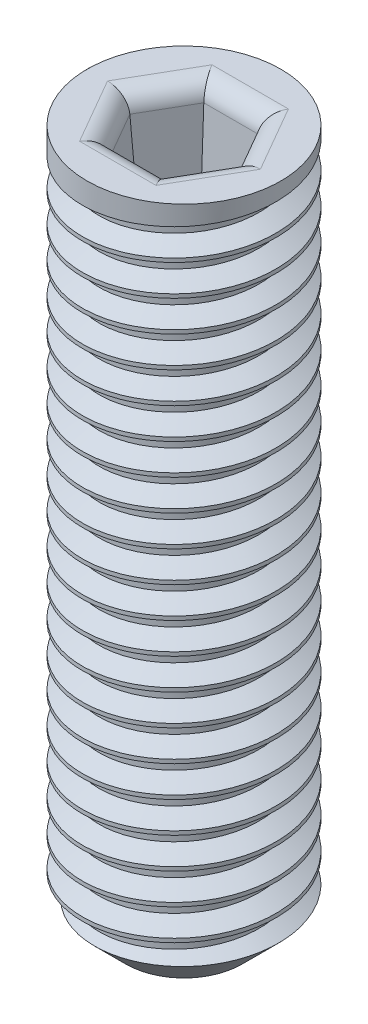
SolidWorks part; units mm, degrees
material "Cast Stainless Steel"
ref_plane "Front Plane" through (0, 0, 0) normal (0, 0, 1) x (1, 0, 0)
ref_plane "Top Plane" through (0, 0, 0) normal (0, 1, 0) x (1, 0, 0)
ref_plane "Right Plane" through (0, 0, 0) normal (1, 0, 0) x (0, 0, -1)
sketch "Sketch1" plane through (0, 0, 0) normal (0, 1, 0) x (1, 0, 0)
  circle A0 centre (0, 0) radius 2.5
  dimension "D1" = 5
extrude "Boss-Extrude1" add sketch "Sketch1" along normal blind 18
chamfer "Chamfer1" distance 1 angle 45 1 edges at (0, 0, 2.5)
sketch "Sketch2" plane through (0, 18, 0) normal (0, 1, 0) x (1, 0, 0)
  line L1 (1.4434, 0) -> (0.7217, 1.25)
  line L2 (0.7217, 1.25) -> (-0.7217, 1.25)
  line L3 (-0.7217, 1.25) -> (-1.4434, 0)
  line L4 (-1.4434, 0) -> (-0.7217, -1.25)
  line L5 (-0.7217, -1.25) -> (0.7217, -1.25)
  line L6 (0.7217, -1.25) -> (1.4434, 0)
  circle A0 centre (0, 0) radius 1.25 construction
  dimension "D1" = 2.5
extrude "Cut-Extrude1" cut sketch "Sketch2" against normal blind 3 draft 5
fillet "Fillet1" radius 0.5 6 edges at (1.0825, 18, -0.625) (1.0825, 18, 0.625) (0, 18, 1.25) (-1.0825, 18, 0.625) (-1.0825, 18, -0.625) (0, 18, -1.25)
thread "Thread1" pitch 0.8 method cut profile "Thread Profile2" start angle 0, offset 0.0001, length 0, pitch 0.8, diameter 5
ref_plane "Plane2" through (-2.5, 17.9999, 0) normal (0, 0, 1) x (-1, 0, 0)
sketch "Thread Profile2" plane through (-2.5, 17.9999, 0) normal (0, 0, 1) x (-1, 0, 0)
  line L0 (0, 0) -> (0, 0.8) construction
  line L11 (0, 0) -> (0, 0.7)
  line L12 (0, 0.7) -> (-0.433, 0.45)
  line L13 (-0.433, 0.45) -> (-0.433, 0.25)
  line L15 (-0.433, 0.25) -> (0, 0)
  line L17 (-0.433, 0.35) -> (0, 0.35) construction
  point P2 (0, 0)
  dimension "Pitch" = 0.8
  dimension "Profile_Angle" = 60
  dimension "Profile_Land" = 0.2
  dimension "Profile_Height" = 0.433
move or copy body "Body-Move/Copy1" [suppressed] bodies to move or copy 103
